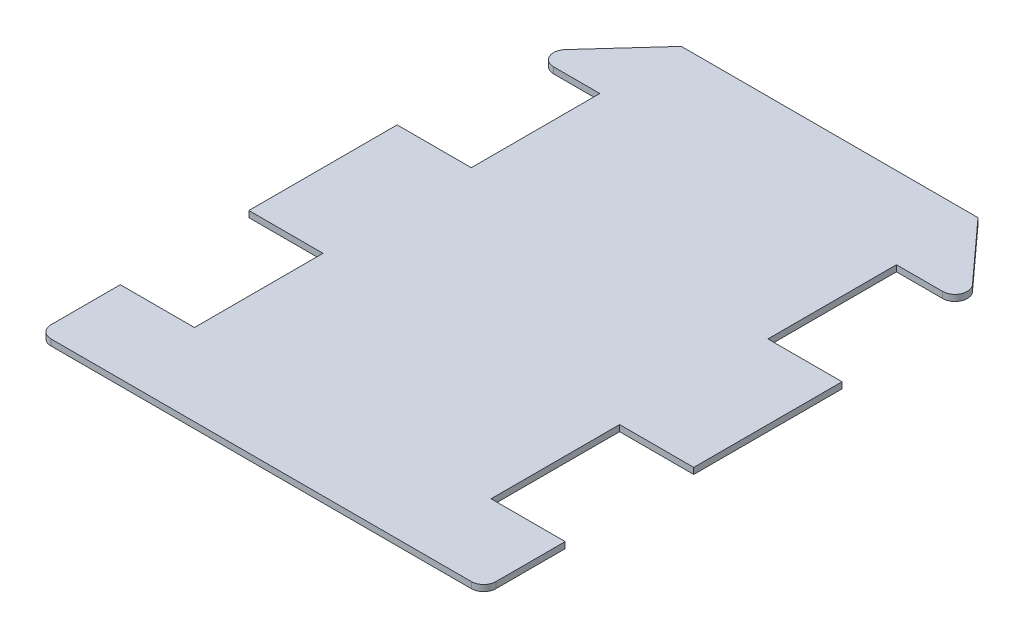
SolidWorks part; units mm, degrees
ref_plane "Front Plane" through (0, 0, 0) normal (0, 0, 1) x (1, 0, 0)
ref_plane "Top Plane" through (0, 0, 0) normal (0, 1, 0) x (1, 0, 0)
ref_plane "Right Plane" through (0, 0, 0) normal (1, 0, 0) x (0, 0, -1)
sketch "Sketch1" plane through (0, 0, 0) normal (0, 1, 0) x (1, 0, 0)
  line L0 (0, 0) -> (0, 60)
  line L1 (0, 60) -> (30, 60)
  line L2 (30, 60) -> (30, 112)
  line L3 (30, 112) -> (0, 112)
  line L4 (0, 112) -> (30, 145)
  line L5 (0, 0) -> (30, 0)
  line L6 (30, 0) -> (30, -52)
  line L7 (30, -52) -> (0, -52)
  line L8 (0, -52) -> (0, -85)
  line L9 (30, 145) -> (150, 145)
  line L10 (0, -85) -> (180, -85)
  line L11 (90, 145) -> (90, -85) construction
  line L12 (180, -52) -> (180, -85)
  line L13 (150, -52) -> (180, -52)
  line L14 (150, 0) -> (150, -52)
  line L15 (180, 0) -> (150, 0)
  line L16 (180, 0) -> (180, 60)
  line L17 (180, 60) -> (150, 60)
  line L18 (150, 60) -> (150, 112)
  line L19 (150, 112) -> (180, 112)
  line L20 (180, 112) -> (150, 145)
  dimension "D1" = 60
  dimension "D2" = 30
  dimension "D3" = 52
  dimension "D4" = 33
  dimension "D5" = 52
  dimension "D6" = 33
  dimension "D7" = 60
  dimension "D8" = 90
extrude "Boss-Extrude1" add sketch "Sketch1" along normal blind 2.5
fillet "Fillet1" radius 5 2 edges at (180, 1.25, 85) (0, 1.25, 85)
fillet "Fillet2" radius 5 2 edges at (0, 1.25, -112) (180, 1.25, -112)
